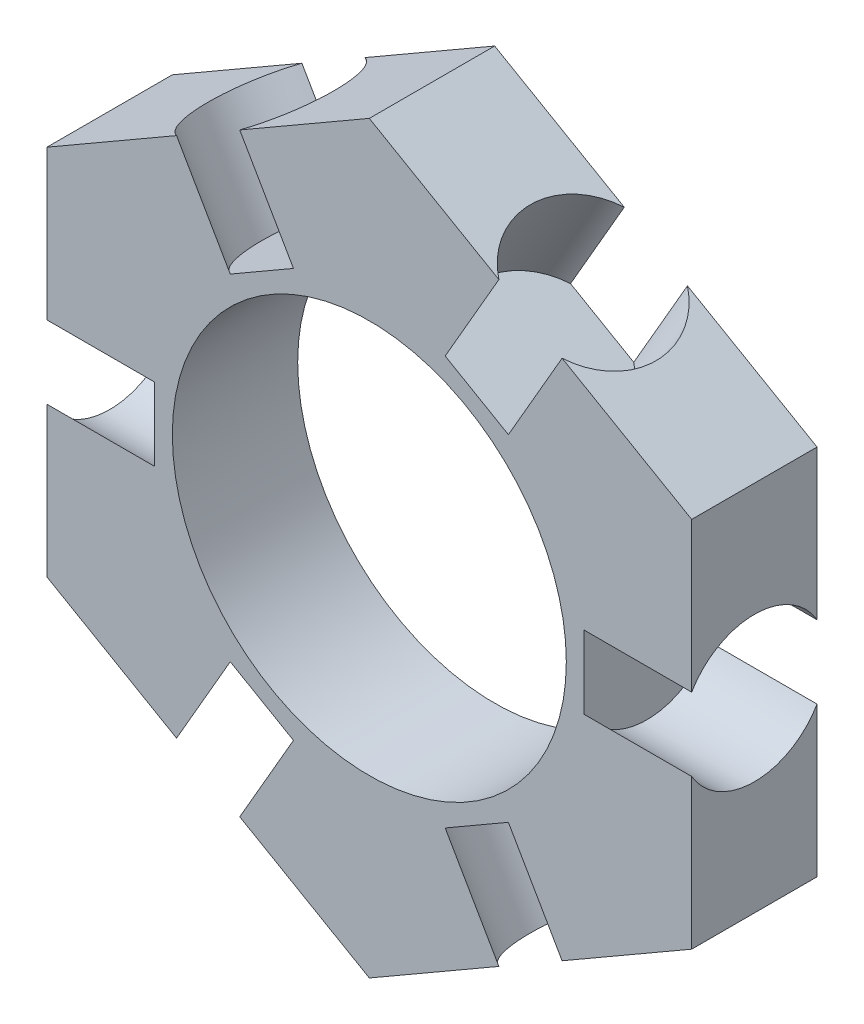
SolidWorks part; units mm, degrees
ref_plane "Top Plane" through (0, 0, 0) normal (0, 0, 1) x (1, 0, 0)
ref_plane "Right Plane" through (0, 0, 0) normal (0, 1, 0) x (1, 0, 0)
ref_plane "Front Plane" through (0, 0, 0) normal (1, 0, 0) x (0, 0, -1)
ref_axis "x-axis" through (-88.99, 0, 0) along (1, 0, 0)
ref_axis "y-axis" through (0, -55, 0) along (0, 1, 0)
ref_axis "z-axis" through (0, 0, 55) along (0, 0, -1)
sketch "Sketch1" plane through (0, 0, 0) normal (0, 0, 1) x (1, 0, 0)
  line L8 (-19.9785, 0) -> (0, 0) construction
  line L16 (0, 0) -> (0, -20.7846) construction
  line L23 (0, 0) -> (0, -20.7846) construction
  line L24 (18, -10.3923) -> (18, 10.3923)
  line L25 (18, 10.3923) -> (0, 20.7846)
  line L26 (0, 20.7846) -> (-18, 10.3923)
  line L27 (-18, 10.3923) -> (-18, -10.3923)
  line L28 (-18, -10.3923) -> (0, -20.7846)
  line L29 (0, -20.7846) -> (18, -10.3923)
  circle A0 centre (0, 0) radius 11
  circle A1 centre (0, 0) radius 18 construction
  dimension "D1" = 22
  dimension "D2" = 7
extrude "Boss-Extrude1" add sketch "Sketch1" along normal mid plane 7
sketch "Sketch2" plane through (-12.6104, -13.504, 0) normal (0.5, 0.866, 0) x (0.866, -0.5, 0)
  circle A0 centre (4.1689, 0) radius 4.05
  dimension "D1" = 8.1
extrude "Cut-Extrude3" cut sketch "Sketch2" along normal blind 6
pattern_circular "CirPattern1" count 6 over 360 about axis through (0, 0, -3.5) along (0, 0, 1) of "Cut-Extrude3"
